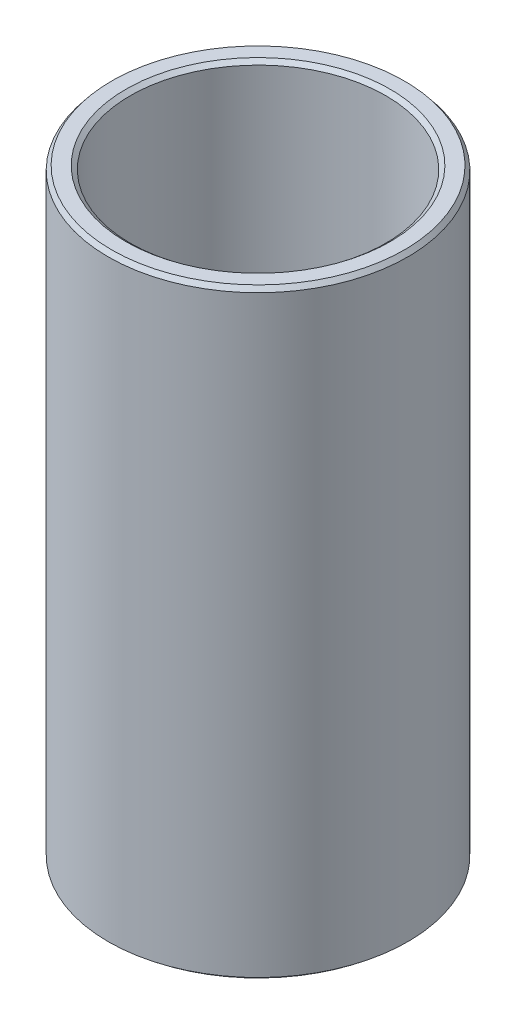
SolidWorks part; units mm, degrees
ref_plane "Front Plane" through (0, 0, 0) normal (0, 0, 1) x (1, 0, 0)
ref_plane "Top Plane" through (0, 0, 0) normal (0, 1, 0) x (1, 0, 0)
ref_plane "Right Plane" through (0, 0, 0) normal (1, 0, 0) x (0, 0, -1)
sketch "Sketch1" plane through (0, 0, 0) normal (0, 1, 0) x (1, 0, 0)
  circle A0 centre (0, 0) radius 27.5
  dimension "SLEEVE_OD" = 55
extrude "Boss-Extrude1" add sketch "Sketch1" along normal blind 110.2974
sketch "Sketch2" plane through (0, 0, 0) normal (0, 1, 0) x (1, 0, 0)
  circle A0 centre (0, 0) radius 23.46
  dimension "BORE_D" = 46.92
extrude "Cut-Extrude1" cut sketch "Sketch2" along normal through all
chamfer "Chamfer1" distance 0.7954 angle 38.683 4 edges at (0, 110.2974, 23.46) (0, 0, 23.46) (0, 0, 27.5) (0, 110.2974, 27.5) first distance on face at (0, 110.2974, 23.46) first distance on face at (0, 0, 23.46) first distance on face at (0, 110.2974, 27.5)
